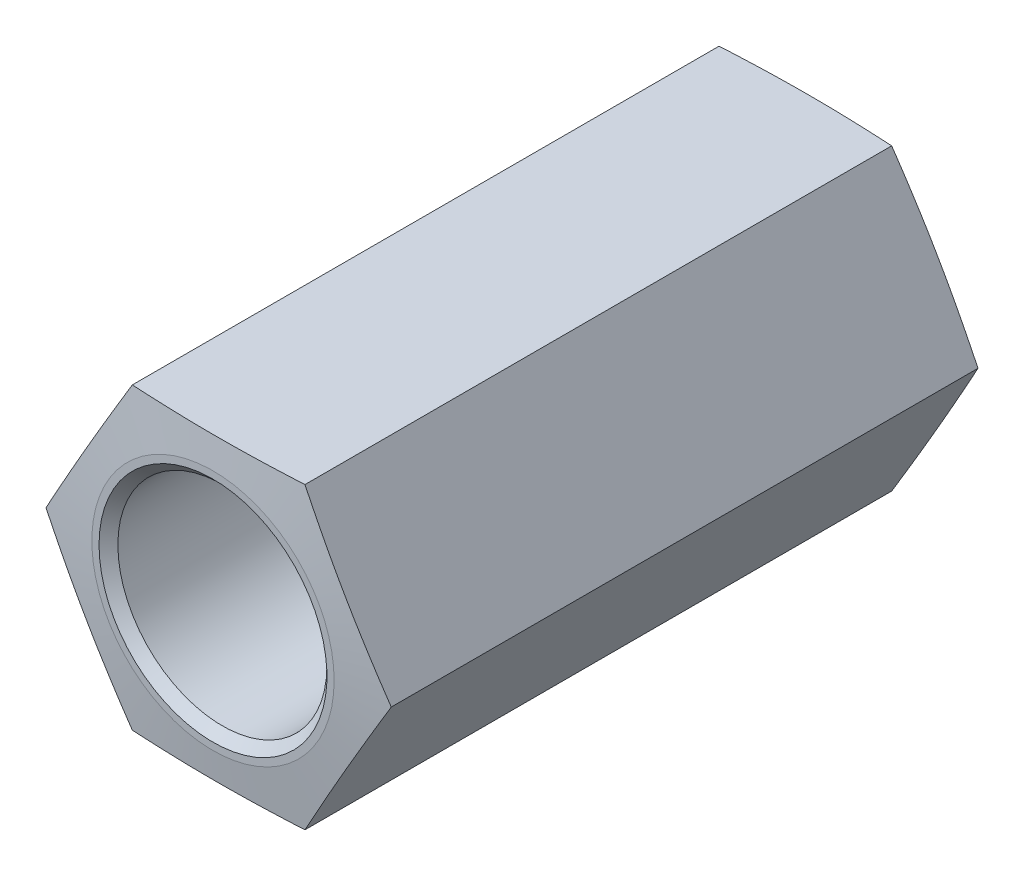
SolidWorks part; units mm, degrees
material "Plain Carbon Steel"
ref_plane "Front Plane" through (0, 0, 0) normal (0, 0, 1) x (1, 0, 0)
ref_plane "Top Plane" through (0, 0, 0) normal (0, 1, 0) x (1, 0, 0)
ref_plane "Right Plane" through (0, 0, 0) normal (1, 0, 0) x (0, 0, -1)
sketch "Sketch1" plane through (0, 0, 0) normal (0, 0, 1) x (1, 0, 0)
  line L0 (-3.6662, 0) -> (-1.8331, -3.175)
  line L1 (-1.8331, -3.175) -> (1.8331, -3.175)
  line L2 (1.8331, -3.175) -> (3.6662, 0)
  line L3 (3.6662, 0) -> (1.8331, 3.175)
  line L4 (1.8331, 3.175) -> (-1.8331, 3.175)
  line L5 (-1.8331, 3.175) -> (-3.6662, 0)
  line L6 (0, 3.175) -> (0, -3.175) construction
  line L7 (-2.7496, 1.5875) -> (0, 0) construction
  circle A0 centre (0, 0) radius 2.22
  point P2 (0, 0)
  dimension "D8" = 4.44
  dimension "D1" = 3.6662
  dimension "D2" = 3.6662
  dimension "D3" = 3.6662
  dimension "D4" = 3.175
  dimension "D5" = 6.35
  dimension "D6" = 7.3323
  dimension "D7" = 3.6662
extrude "Extrude1" add sketch "Sketch1" along normal mid plane 12.7
cosmetic thread "Cosmetic Thread1" parameters "D2"=5
chamfer "Chamfer1" distance 0.2 angle 45 2 edges at (2.22, 0, -6.35) (2.22, 0, 6.35)
ref_plane "Plane1" through (0, 0, 0) normal (0, 1, 0) x (-1, 0, 0)
sketch "Sketch2" plane through (0, 0, 0) normal (0, -1, 0) x (1, 0, 0)
  line L0 (-2.5727, -6.35) -> (-3.6662, -6.23)
  line L3 (-3.6662, -6.23) -> (-3.6662, -6.35)
  line L4 (-3.6662, -6.35) -> (-2.5727, -6.35)
  dimension "D1" = 1.0934
  dimension "D2" = 0.12
revolve "Cut-Revolve1" cut sketch "Sketch2" angle 360 about axis through (0, 0, 6.35) along (0, 0, -1)
mirror "Mirror1" about plane through (0, 0, 0) normal (0, 0, 1) of "Cut-Revolve1"
ref_axis "Axis1" through (0, 0, -8.7639) along (0, 0, 1)
